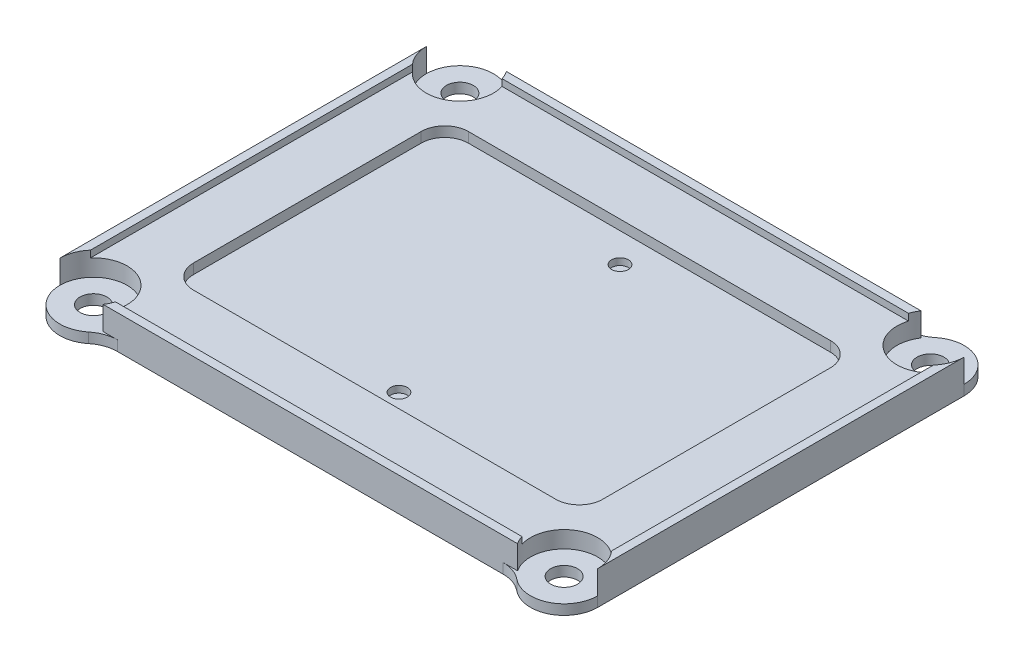
SolidWorks part; units mm, degrees
ref_plane "Front Plane" through (0, 0, 0) normal (0, 0, 1) x (1, 0, 0)
ref_plane "Top Plane" through (0, 0, 0) normal (0, 1, 0) x (1, 0, 0)
ref_plane "Right Plane" through (0, 0, 0) normal (1, 0, 0) x (0, 0, -1)
sketch "Sketch1" plane through (0, 0, 0) normal (0, 1, 0) x (1, 0, 0)
  line L0 (-70, 54.5) -> (66.8873, 54.5) construction
  line L1 (80, -64.5) -> (-80, -64.5)
  line L2 (80, -64.5) -> (80, 64.5)
  line L3 (80, 64.5) -> (-80, 64.5)
  line L4 (-80, -64.5) -> (-80, 64.5)
  line L5 (0, 64.5) -> (0, -64.5) construction
  line L6 (80, 0) -> (-80, 0) construction
  line L7 (53.875, -40.875) -> (-53.875, -40.875)
  line L8 (60.875, -33.875) -> (60.875, 33.875)
  line L9 (53.875, 40.875) -> (-53.875, 40.875)
  line L10 (-60.875, -33.875) -> (-60.875, 33.875)
  line L11 (0, 40.875) -> (0, -40.875) construction
  line L12 (60.875, 0) -> (-60.875, 0) construction
  line L13 (-70, 50.5) -> (-48.7993, 50.5) construction
  line L14 (-70, -50.5) -> (-35.916, -50.5) construction
  line L15 (-70, 50.5) -> (-70, -50.5) construction
  line L16 (-70, -54.5) -> (66.8873, -54.5) construction
  line L17 (-67.2741, 57.5) -> (-72.6458, 57.5)
  line L18 (77.5, -57.5) -> (-77.5, -57.5)
  line L19 (77.5, -57.5) -> (77.5, 57.5)
  line L20 (77.5, 57.5) -> (-62.5, 57.5)
  line L21 (-77.5, -57.5) -> (-77.5, 57.5)
  line L22 (0, 57.5) -> (0, -57.5) construction
  line L23 (77.5, 0) -> (-77.5, 0) construction
  line L24 (-77.5, 57.5) -> (-72.6458, 57.5)
  line L25 (-67.2741, 57.5) -> (-62.5, 57.5)
  line L26 (-61.6484, 60) -> (61.6484, 60)
  line L27 (-61.6484, -60) -> (61.6484, -60)
  arc A0 (-60.875, -33.875) -> (-53.875, -40.875) centre (-53.875, -33.875) ccw
  arc A1 (60.875, -33.875) -> (53.875, -40.875) centre (53.875, -33.875) cw
  arc A2 (60.875, 33.875) -> (53.875, 40.875) centre (53.875, 33.875) ccw
  arc A3 (-53.875, 40.875) -> (-60.875, 33.875) centre (-53.875, 33.875) ccw
  circle A4 centre (0, 32.125) radius 2.5
  circle A6 centre (-70, 54.5) radius 4
  circle A7 centre (-70, -54.5) radius 4
  circle A8 centre (70, -54.5) radius 4
  circle A9 centre (70, 54.5) radius 4
  circle A16 centre (-70, 54.5) radius 10
  circle A17 centre (70, 54.5) radius 10
  circle A18 centre (-70, -54.5) radius 10
  circle A19 centre (70, -54.5) radius 10
  circle A21 centre (0, -33.625) radius 2.5
  point P0 (0, 0)
  point P4 (0, 0)
  point P10 (-60.875, -40.875)
  point P16 (60.875, 40.875)
  point P19 (-60.875, 40.875)
  point P33 (-70, 0)
  point P34 (0, 0)
  point P39 (-70, 58.5)
  point P44 (70, 58.5)
  point P54 (0, 0)
  point P55 (0, 0)
  dimension "D5" = 7
  dimension "D6" = 5
  dimension "D8" = 2.5
  dimension "D9" = 8
  dimension "D14" = 5
  dimension "D1" = 129
  dimension "D2" = 160
  dimension "D3" = 121.75
  dimension "D4" = 81.75
  dimension "D7" = 8.75
  dimension "D10" = 101
  dimension "D11" = 70
  dimension "D12" = 155
  dimension "D13" = 115
  dimension "D15" = 7.25
extrude "Boss-Extrude1" add sketch "Sketch1" along normal blind 8 contours L1 L4 L3 L2
extrude "Cut-Extrude2" cut sketch "Sketch1<3>" along normal through all contours A6 | A9 | A8 | A7
sketch "Sketch1<3>" plane through (0, 0, 0) normal (0, 1, 0) x (1, 0, 0) same geometry as "Sketch1"
fillet "Fillet1" radius 10 4 edges at (80, 4, 64.5) (-80, 4, 64.5) (-80, 4, -64.5) (80, 4, -64.5)
extrude "Cut-Extrude4" cut sketch "Sketch1<11>" against normal blind 3 and the other way blind 1 from surface contours L9 A3 L10 A0 L7 A1 L8 A2 starting at face at (-70, 8, 58.5)
sketch "Sketch1<11>" plane through (0, 0, 0) normal (0, 1, 0) x (1, 0, 0) same geometry as "Sketch1"
extrude "Cut-Extrude9" cut sketch "Sketch1<13>" along normal through all contours A19 L27 A18 L1 | A17 L3 A16 L26 region at (0, 0, 62.2876) region at (0, 0, -62.2876)
sketch "Sketch1<13>" plane through (0, 0, 0) normal (0, 1, 0) x (1, 0, 0) same geometry as "Sketch1"
extrude "Cut-Extrude10" cut sketch "Sketch1<17>" against normal blind 5 from surface contours A16 | A18 | A19 | A17 | A4 | A21 starting at face at (0, 8, 0)
sketch "Sketch1<17>" plane through (0, 0, 0) normal (0, 1, 0) x (1, 0, 0) same geometry as "Sketch1"
extrude "Boss-Extrude4" add sketch "Sketch1<18>" along normal blind 10 contours A17 L26 A16 L20 | A18 L21 A16 L4 | A19 L2 A17 L19 | A19 L18 A18 L27 region at (78.7716, 0, 0) region at (0, 0, 58.754) region at (-78.7716, 0, 0) region at (0, 0, -58.754)
sketch "Sketch1<18>" plane through (0, 0, 0) normal (0, 1, 0) x (1, 0, 0) same geometry as "Sketch1"
fillet "Fillet2" radius 10 4 edges at (61.6484, 1.5, 60) (-61.6484, 1.5, 60) (61.6484, 1.5, -60) (-61.6484, 1.5, -60)
